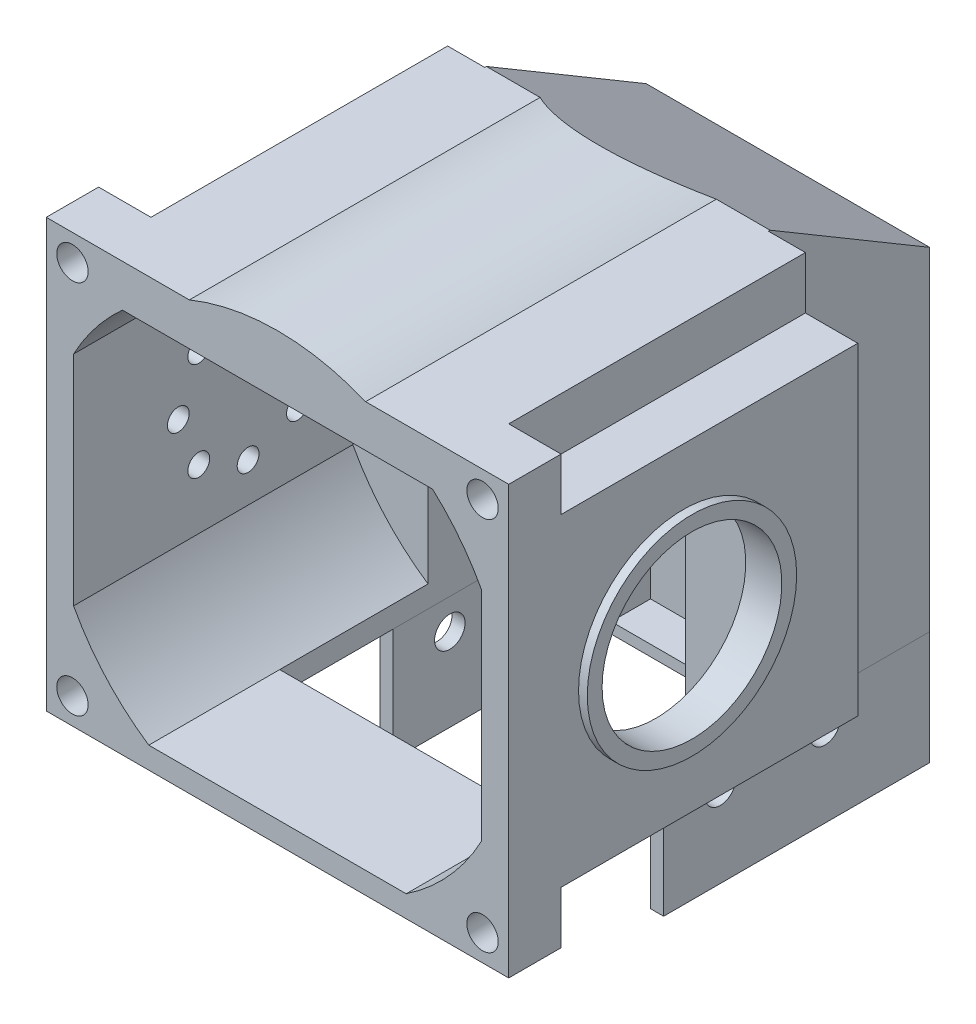
SolidWorks part; units mm, degrees
ref_plane "Front Plane" through (0, 0, 0) normal (0, 0, 1) x (1, 0, 0)
ref_plane "Top Plane" through (0, 0, 0) normal (0, 1, 0) x (1, 0, 0)
ref_plane "Right Plane" through (0, 0, 0) normal (1, 0, 0) x (0, 0, -1)
sketch "Sketch1" plane through (0, 0, 0) normal (0, 0, 1) x (1, 0, 0)
  circle A0 centre (0, 0) radius 26.5
  dimension "D1" = 53
extrude "Boss-Extrude1" add sketch "Sketch1" along normal blind 8
sketch "Sketch2" plane through (0, 0, 0) normal (0, 0, -1) x (-1, 0, 0)
  line L0 (0, 0) -> (0, 6.7026)
  line L1 (-26.5, 12.5) -> (-23.3666, 12.5)
  line L2 (-26.5, 12.5) -> (-26.5, -12.5)
  line L3 (-26.5, -12.5) -> (-23.3666, -12.5)
  line L4 (-23.3666, 12.5) -> (-23.3666, -12.5)
  line L5 (-24.9333, -12.5) -> (-24.9333, 12.5) construction
  line L6 (-26.5, 0) -> (-23.3666, 0) construction
  line L7 (26.5, 0) -> (23.3666, 0) construction
  line L8 (24.9333, -12.5) -> (24.9333, 12.5) construction
  line L9 (26.5, -12.5) -> (23.3666, -12.5)
  line L10 (23.3666, 12.5) -> (23.3666, -12.5)
  line L11 (26.5, 12.5) -> (23.3666, 12.5)
  line L12 (26.5, 12.5) -> (26.5, -12.5)
  circle A0 centre (0, 0) radius 26.5 construction
  point P0 (-24.9333, 0)
  circle M8 centre (0, 0) radius 26.5
  dimension "D1" = 26.5
  dimension "D2" = 25
extrude "Boss-Extrude4" add sketch "Sketch2" against normal blind 40 contours L10 M8 | L12 L9 M8 | L12 L11 M8 | L2 L3 L4 L1 region at (-24.6266, 0, 0) region at (-25.5704, 9.4132, 0) region at (-25.5704, -9.4132, 0)
sketch "Sketch3" plane through (0, 0, 0) normal (0, 0, -1) x (-1, 0, 0)
  line L0 (-26.5, 12.5) -> (-26.5, 24.5)
  line L1 (-26.5, 24.5) -> (-10.0995, 24.5)
  line L2 (-26.5, 12.5) -> (-10.0995, 12.5)
  line L3 (-10.0995, 12.5) -> (-10.0995, 24.5)
  line L4 (-26.5, -12.5) -> (-26.5, -24.5)
  line L5 (-26.5, -24.5) -> (-10.0995, -24.5)
  line L6 (-10.0995, -24.5) -> (-10.0995, -12.5)
  line L7 (-10.0995, -12.5) -> (-26.5, -12.5)
  line L8 (0, 0) -> (0, 7.9351)
  line L9 (10.0995, -24.5) -> (10.0995, -12.5)
  line L10 (26.5, -24.5) -> (10.0995, -24.5)
  line L11 (26.5, -12.5) -> (26.5, -24.5)
  line L12 (10.0995, -12.5) -> (26.5, -12.5)
  line L13 (26.5, 12.5) -> (10.0995, 12.5)
  line L14 (26.5, 12.5) -> (26.5, 24.5)
  line L15 (26.5, 24.5) -> (10.0995, 24.5)
  line L16 (10.0995, 12.5) -> (10.0995, 24.5)
  line L17 (-10.0995, 22) -> (10.0995, 22)
  arc A0 (23.3666, 12.5) -> (-23.3666, 12.5) centre (0, 0) ccw construction
  arc A1 (-23.3666, -12.5) -> (23.3666, -12.5) centre (0, 0) ccw construction
  arc A2 (-10.0995, 24.5) -> (10.0995, 24.5) centre (0, 0) cw
  arc M10 (23.3666, 12.5) -> (-23.3666, 12.5) centre (0, 0) ccw
  line M11 (-23.3666, 12.5) -> (-26.5, 12.5)
  line M13 (-26.5, -12.5) -> (-23.3666, -12.5)
  arc M14 (-23.3666, -12.5) -> (23.3666, -12.5) centre (0, 0) ccw
  line M15 (23.3666, -12.5) -> (26.5, -12.5)
  line M17 (26.5, 12.5) -> (23.3666, 12.5)
  dimension "D1" = 12
  dimension "12" = 12
  dimension "D2" = 2.5
extrude "Boss-Extrude5" add sketch "Sketch3" against normal blind 40 contours L1 L0 M11 M10 | L4 L5 M14 M13 | L14 L15 M10 M17 | L11 L10 M15 M14 region at (21.5689, 20.028, 0) region at (-21.5689, 20.028, 0) region at (21.5689, -20.028, 0) region at (-21.5689, -20.028, 0)
sketch "Sketch4" plane through (0, 0, 0) normal (0, 0, -1) x (-1, 0, 0)
  line L1 (-16.25, 24.5) -> (16.25, 24.5)
  line L2 (-16.25, 24.5) -> (-16.25, -24.5)
  line L3 (-16.25, -24.5) -> (16.25, -24.5)
  line L4 (16.25, 24.5) -> (16.25, -24.5)
  line L5 (0, -24.5) -> (0, 24.5) construction
  line L6 (-16.25, 0) -> (16.25, 0) construction
  point P0 (0, 0)
  dimension "D1" = 49
  dimension "D2" = 32.5
extrude "Boss-Extrude7" add sketch "Sketch4" along normal blind 18.5
sketch "Sketch7" plane through (0, 0, 0) normal (0, 0, -1) x (-1, 0, 0)
  line L0 (-10.0995, 24.5) -> (9.9053, 24.5)
  line L1 (10.0995, -24.5) -> (-10.0995, -24.5)
  arc A0 (10.0995, -24.5) -> (-10.0995, -24.5) centre (0, 0) cw
  line M1 (-10.0995, 24.5) -> (10.0995, 24.5)
  arc M2 (10.0995, 24.5) -> (-10.0995, 24.5) centre (0, 0) ccw
extrude "Boss-Extrude9" add sketch "Sketch7" along normal blind 18.5 contours A0 L1 | M2 M1 region at (0, 25.3026, 0) region at (0, -25.3026, 0)
sketch "Sketch8" plane through (0, 0, 8) normal (0, 0, 1) x (1, 0, 0)
  line L2 (-14.75, -36.25) -> (14.75, -36.25)
  line L3 (-14.75, -36.25) -> (-14.75, 11.25)
  line L4 (-14.75, 11.25) -> (14.75, 11.25)
  line L5 (14.75, -36.25) -> (14.75, 11.25)
  line L6 (0, 11.25) -> (0, -36.25) construction
  line L7 (-14.75, -12.5) -> (14.75, -12.5) construction
  circle A0 centre (0, 0) radius 2.6374
  point P3 (0, -12.5)
  arc M4 (-23.3666, -12.5) -> (-10.0995, -24.5) centre (0, 0) ccw
  arc M5 (-10.0995, -24.5) -> (10.0995, -24.5) centre (0, 0) ccw
  arc M6 (10.0995, -24.5) -> (23.3666, -12.5) centre (0, 0) ccw
  dimension "D1" = 11.25
  dimension "D2" = 47.5
  dimension "D3" = 0
  dimension "D4" = 29.5
sketch "Sketch10" plane through (0, 0, -18.5) normal (0, 0, -1) x (-1, 0, 0)
  line L7 (16.25, -24.5) -> (16.25, -37.5)
  line L8 (16.25, -37.5) -> (-10.0995, -37.5)
  line L9 (-10.0995, -37.5) -> (-16.25, -37.5)
  line L10 (-16.25, -37.5) -> (-16.25, -24.5)
  line L13 (16.25, -24.5) -> (16.25, 24.5)
  line L14 (16.25, 24.5) -> (10.0995, 24.5)
  line L16 (-16.25, 24.5) -> (-16.25, -24.5)
  line L17 (-16.25, -24.5) -> (-10.0995, -24.5)
  line L18 (10.0995, -24.5) -> (16.25, -24.5)
  line L23 (-16.25, -24.5) -> (-10.0995, -24.5)
  line L24 (10.0995, -24.5) -> (16.25, -24.5)
  line L26 (-10.0995, 24.5) -> (-16.25, 24.5)
  arc A2 (10.0995, 24.5) -> (-10.0995, 24.5) centre (0, 0) ccw
  arc A3 (-10.0995, -24.5) -> (10.0995, -24.5) centre (0, 0) ccw
  arc A11 (-10.0995, -24.5) -> (10.0995, -24.5) centre (0, 0) ccw
  dimension "D1" = 13
  dimension "D4" = 0
extrude "Boss-Extrude13" add sketch "Sketch10" against normal blind 30.5 separate body
extrude "Cut-Extrude2" cut sketch "Sketch8" against normal blind 25.5 and the other way blind 40 contours A0 | L5 L4 L3 A0 M6 M4 M5 | L2 L5 L3 M6 M5 M4 region at (0, -30.5773, 8) region at (0, -7.0731, 8) region at (0, 0, 8)
sketch "Sketch12" plane through (0, 0, 40) normal (0, 0, 1) x (1, 0, 0)
  line L0 (14.75, -24.5) -> (-14.75, -24.5)
  line L1 (-14.75, -24.5) -> (-14.75, -22.0156)
  line L2 (-14.75, -22.0156) -> (14.75, -22.0156)
  line L3 (14.75, -22.0156) -> (14.75, -24.5)
extrude "Boss-Extrude14" add sketch "Sketch12" against normal blind 15
sketch "Sketch15" plane through (16.25, 0, 0) normal (1, 0, 0) x (0, 0, -1)
  line L0 (18.5, 24.5) -> (18.5, -4)
  circle A0 centre (6.5, -4) radius 1.75
  circle A1 centre (-5.5, -4) radius 1.75
  circle A2 centre (-5.5, -28) radius 1.75
  circle A3 centre (6.5, -28) radius 1.75
  dimension "D3" = 3.5
  dimension "D4" = 3.5
  dimension "D1" = 28.5
  dimension "D2" = 12
  dimension "D5" = 12
  dimension "D6" = 2
extrude "Cut-Extrude3" cut sketch "Sketch15" against normal blind 40 contours A3 | A2 | A0 | A1
sketch "Sketch18" plane through (26.5, 0, 0) normal (1, 0, 0) x (0, 0, -1)
  line L1 (0, 24.5) -> (0, -24.5) construction
  circle A0 centre (-20, 0) radius 10.3
  dimension "D1" = 20.6
  dimension "D2" = 20
sketch "Sketch21" plane through (-26.5, 0, 0) normal (-1, 0, 0) x (0, 0, 1)
  line L0 (40, -24.5) -> (0, -24.5) construction
  line L1 (40, 24.5) -> (40, -24.5) construction
  circle A0 centre (20, 0) radius 1.4223
  circle A1 centre (20, 8) radius 1.25
  circle A2 centre (25.6569, 5.6569) radius 1.25
  circle A3 centre (28, 0) radius 1.25
  circle A4 centre (25.6569, -5.6569) radius 1.25
  circle A5 centre (20, -8) radius 1.25
  circle A6 centre (14.3431, -5.6569) radius 1.25
  circle A7 centre (12, 0) radius 1.25
  circle A8 centre (14.3431, 5.6569) radius 1.25
  dimension "D3" = 2.5
  dimension "D1" = 20
  dimension "D2" = 8
  dimension "D4" = 8
extrude "Cut-Extrude10" cut sketch "Sketch21" against normal blind 7 contours A4 | A1 | A5 | A6 | A7 | A8 | A2 | A3 region at (-26.5, 8, 20) region at (-26.5, -5.6569, 25.6569)
sketch "Sketch22" plane through (0, 0, 8) normal (0, 0, 1) x (1, 0, 0)
  line L0 (17.7763, 19.6534) -> (-17.7763, 19.6534)
  arc A0 (23.3666, 12.5) -> (10.0995, 24.5) centre (0, 0) ccw construction
  arc A1 (-10.0995, 24.5) -> (-23.3666, 12.5) centre (0, 0) ccw construction
  arc A2 (-17.7763, 19.6534) -> (17.7763, 19.6534) centre (0, 0) cw
extrude "Boss-Extrude16" add sketch "Sketch22" along normal up to surface (32 mm away) up to face at (0, 0.518, 40)
sketch "Sketch23" plane through (26.5, 0, 0) normal (1, 0, 0) x (0, 0, -1)
  line L0 (-40, 24.5) -> (0, 24.5) construction
  line L1 (-34, 24.5) -> (1, 24.5)
  line L2 (-34, 24.5) -> (-34, 18.5)
  line L3 (-34, 18.5) -> (1, 18.5)
  line L4 (1, 24.5) -> (1, 18.5)
  line L5 (-40, 24.5) -> (-40, -24.5) construction
  line L6 (-34, -18.5) -> (-34, -24.5)
  line L7 (-34, -18.5) -> (1, -18.5)
  line L8 (1, -18.5) -> (1, -24.5)
  line L9 (-34, -24.5) -> (1, -24.5)
  dimension "D1" = 6
  dimension "D2" = 35
  dimension "D3" = 6
  dimension "D4" = 2
extrude "Cut-Extrude12" cut sketch "Sketch23" against normal blind 6
sketch "Sketch24" plane through (-26.5, 0, 0) normal (-1, 0, 0) x (0, 0, 1)
  line L0 (40, -24.5) -> (0, -24.5) construction
  line L1 (34, -24.5) -> (-1, -24.5)
  line L2 (34, -24.5) -> (34, -18.5)
  line L3 (34, -18.5) -> (-1, -18.5)
  line L4 (-1, -24.5) -> (-1, -18.5)
  line L5 (40, 24.5) -> (40, -24.5) construction
  line L6 (34, 18.5) -> (34, 24.5)
  line L7 (34, 18.5) -> (-1, 18.5)
  line L8 (-1, 18.5) -> (-1, 24.5)
  line L9 (34, 24.5) -> (-1, 24.5)
  dimension "D1" = 6
  dimension "D2" = 35
  dimension "D3" = 6
  dimension "D4" = 2
extrude "Cut-Extrude13" cut sketch "Sketch24" against normal blind 6
sketch "Sketch26" plane through (0, 0, -17.5) normal (0, 0, 1) x (1, 0, 0)
  line L0 (14.75, -36.25) -> (14.75, -22.25)
  line L1 (14.75, -24.5) -> (14.75, 11.25) construction
  line L2 (0, 0) -> (0, -8.75)
  line L3 (14.75, -22.25) -> (9.75, -22.25)
  line L4 (14.75, -22.25) -> (14.75, -7.25)
  line L5 (14.75, -7.25) -> (9.75, -7.25)
  line L6 (9.75, -22.25) -> (9.75, -7.25)
  line L7 (-14.75, -7.25) -> (-9.75, -7.25)
  line L8 (-9.75, -22.25) -> (-9.75, -7.25)
  line L9 (-14.75, -22.25) -> (-9.75, -22.25)
  line L10 (-14.75, -22.25) -> (-14.75, -7.25)
  dimension "D1" = 14
  dimension "D2" = 5
  dimension "D3" = 15
extrude "Cut-Extrude14" cut sketch "Sketch26" against normal blind 6 contours L3 L6 L5 L4 | L8 L7 L10 L9
sketch "Sketch27" plane through (0, 0, 40) normal (0, 0, 1) x (1, 0, 0)
  line L0 (-26.5, 21.5) -> (-23.5, 21.5)
  line L1 (-26.5, 24.5) -> (-26.5, -24.5) construction
  line L2 (-23.5, 21.5) -> (-23.5, 24.5)
  line L3 (-26.5, 24.5) -> (-10.0995, 24.5) construction
  line L6 (0, 0) -> (11.4421, 0)
  circle A0 centre (-23.5, 21.5) radius 1.8
  circle A1 centre (23.5, 21.5) radius 1.8
  circle A2 centre (23.5, -21.5) radius 1.8
  circle A3 centre (-23.5, -21.5) radius 1.8
  dimension "D3" = 3.6
  dimension "D1" = 3
  dimension "D2" = 3
  dimension "D4" = 2
extrude "Cut-Extrude15" cut sketch "Sketch27" against normal blind 6 contours A3 | A0 | A1 | A2
extrude "Cut-Extrude16" cut sketch "Sketch18" against normal blind 5 and the other way through all
sketch "Sketch28" plane through (0, 0, 8) normal (0, 0, 1) x (1, 0, 0)
  line L0 (14.75, 11.25) -> (14.75, 19.6534)
  line L1 (-17.7763, 19.6534) -> (17.7763, 19.6534) construction
  line L2 (-14.75, 11.25) -> (-14.75, 19.6534)
  line L3 (-14.75, 19.6534) -> (14.75, 19.6534)
  line L4 (14.75, 11.25) -> (-14.75, 11.25)
extrude "Cut-Extrude17" cut sketch "Sketch28" against normal blind 15
sketch "Sketch29" plane through (26.5, 0, 0) normal (1, 0, 0) x (0, 0, -1)
  circle A0 centre (-20, 0) radius 12
  dimension "D1" = 24
extrude "Boss-Extrude17" add sketch "Sketch29" along normal blind 1
sketch "Sketch30" plane through (27.5, 0, 0) normal (1, 0, 0) x (0, 0, -1)
  circle A0 centre (-20, 0) radius 10
  dimension "D1" = 20
extrude "Cut-Extrude18" cut sketch "Sketch30" against normal blind 21 and the other way through all
sketch "Sketch32" plane through (16.25, 0, 0) normal (1, 0, 0) x (0, 0, -1)
  line L1 (18.5, 24.5) -> (18.5, -24.5) construction
  line L3 (18.5, 13.6407) -> (-3.179, 26.5)
  line L4 (18.5, 26.5) -> (-40, 26.5) construction
  line L5 (-3.179, 26.5) -> (18.5, 26.5)
  line L6 (18.5, 26.5) -> (18.5, 13.6407)
extrude "Cut-Extrude19" cut sketch "Sketch32" against normal through all
sketch "Sketch33" plane through (0, 0, 12) normal (0, 0, 1) x (1, 0, 0)
  line L0 (-14.75, -36.25) -> (-14.75, -37.5)
  line L1 (16.25, -37.5) -> (-16.25, -37.5) construction
  line L2 (-14.75, -36.25) -> (14.75, -36.25)
  line L3 (-14.75, -36.25) -> (14.75, -36.25) construction
  line L4 (14.75, -36.25) -> (14.75, -37.5)
  line L5 (14.75, -37.5) -> (-14.75, -37.5)
extrude "Cut-Extrude20" cut sketch "Sketch33" against normal blind 25
sketch "Sketch34" plane through (27.5, 0, 0) normal (1, 0, 0) x (0, 0, -1)
  circle A0 centre (-20, 0) radius 10.3
  dimension "D1" = 20.6
extrude "Cut-Extrude21" cut sketch "Sketch34" against normal blind 11
